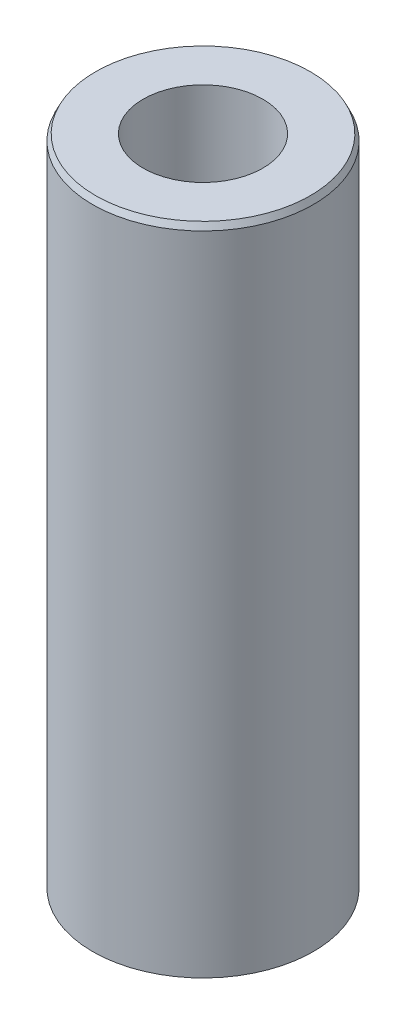
SolidWorks part; units mm, degrees
ref_plane "Front Plane" through (0, 0, 0) normal (0, 0, 1) x (1, 0, 0)
ref_plane "Top Plane" through (0, 0, 0) normal (0, 1, 0) x (1, 0, 0)
ref_plane "Right Plane" through (0, 0, 0) normal (1, 0, 0) x (0, 0, -1)
sketch "Sketch1" plane through (0, 0, 0) normal (0, 1, 0) x (1, 0, 0)
  circle A0 centre (0, 0) radius 17.5
  dimension "SHAFT_OD" = 35
extrude "Boss-Extrude1" add sketch "Sketch1" along normal blind 104.0138
sketch "Sketch2" plane through (0, 0, 0) normal (0, 1, 0) x (1, 0, 0)
  circle A0 centre (0, 0) radius 9.4854
  dimension "BORE_D" = 18.9709
extrude "Cut-Extrude1" cut sketch "Sketch2" along normal through all
chamfer "Chamfer1" distance 0.9895 angle 25.683 2 edges at (0, 104.0138, 17.5) (0, 0, 17.5) first distance on face at (0, 104.0138, 17.5) first distance on face at (0, 0, 9.4854)
